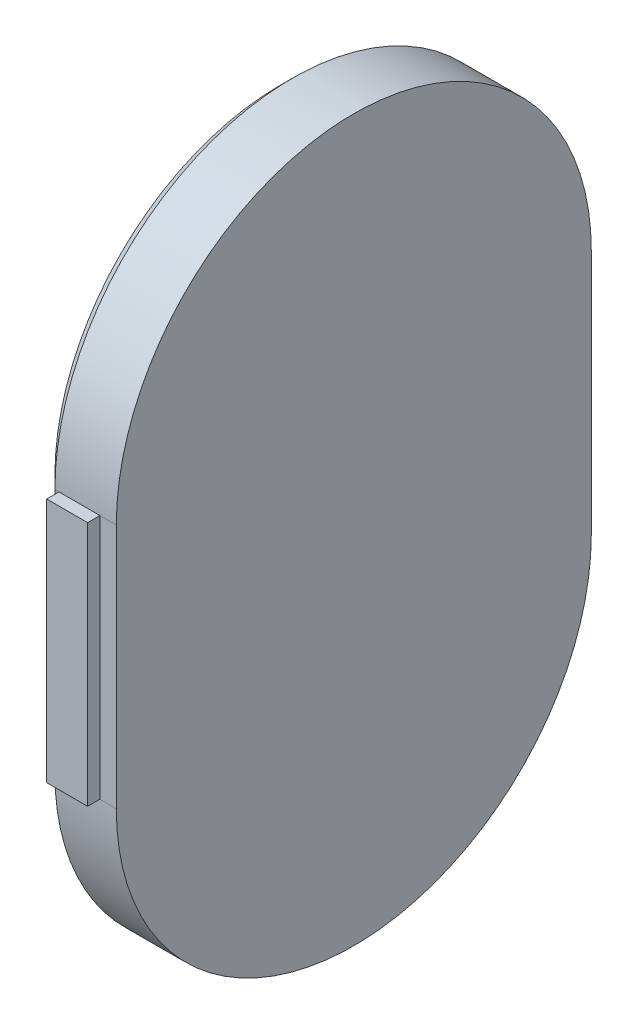
SolidWorks part; units mm, degrees
ref_plane "Front Plane" through (0, 0, 0) normal (0, 0, 1) x (1, 0, 0)
ref_plane "Top Plane" through (0, 0, 0) normal (0, 1, 0) x (1, 0, 0)
ref_plane "Right Plane" through (0, 0, 0) normal (1, 0, 0) x (0, 0, -1)
sketch "Sketch1" plane through (0, 0, 0) normal (1, 0, 0) x (0, 0, -1)
  line L0 (-94.1, 53) -> (-94.1, 59)
  line L1 (-82.5, 59) -> (-82.5, 53)
  arc A0 (-82.5, 53) -> (-88.3, 47.2) centre (-88.3, 53) cw
  arc A1 (-88.3, 47.2) -> (-94.1, 53) centre (-88.3, 53) cw
  arc A2 (-94.1, 59) -> (-88.3, 64.8) centre (-88.3, 59) cw
  arc A3 (-88.3, 64.8) -> (-82.5, 59) centre (-88.3, 59) cw
extrude "Boss-Extrude1" add sketch "Sketch1" along normal blind 1.8 from offset 38 offset against normal yes
chamfer "Chamfer1" distance 0.3 angle 45 4 edges at (-38, 47.2, 88.3) (-38, 56, 82.5) (-38, 56, 94.1) (-38, 64.8, 88.3)
sketch "Sketch2" plane through (0, 0, 0) normal (0, 0, 1) x (1, 0, 0)
  line L1 (-37.6, 53) -> (-36.6, 53)
  line L2 (-37.6, 53) -> (-37.6, 59)
  line L3 (-37.6, 59) -> (-36.6, 59)
  line L4 (-36.6, 53) -> (-36.6, 59)
extrude "Boss-Extrude2" add sketch "Sketch2" along normal blind 0.31 from offset 82.2
sketch "Sketch3" plane through (0, 0, 0) normal (0, 0, 1) x (1, 0, 0)
  line L1 (-37.6, 53) -> (-36.6, 53)
  line L2 (-37.6, 53) -> (-37.6, 59)
  line L3 (-37.6, 59) -> (-36.6, 59)
  line L4 (-36.6, 53) -> (-36.6, 59)
extrude "Boss-Extrude3" add sketch "Sketch3" along normal blind 0.31 from offset 94.09
sketch "Sketch4" plane through (0, 0, 0) normal (0, 0, 1) x (1, 0, 0)
  line L1 (-38.1, 47.1) -> (-37.4, 47.1)
  line L2 (-38.1, 47.1) -> (-38.1, 48.4)
  line L3 (-38.1, 48.4) -> (-37.4, 48.4)
  line L4 (-37.4, 47.1) -> (-37.4, 48.4)
extrude "Boss-Extrude4" add sketch "Sketch4" along normal blind 3 from offset 86.8 separate body
combine bodies "Combine1" operation type subtract main body 103 bodies to subtract 104
